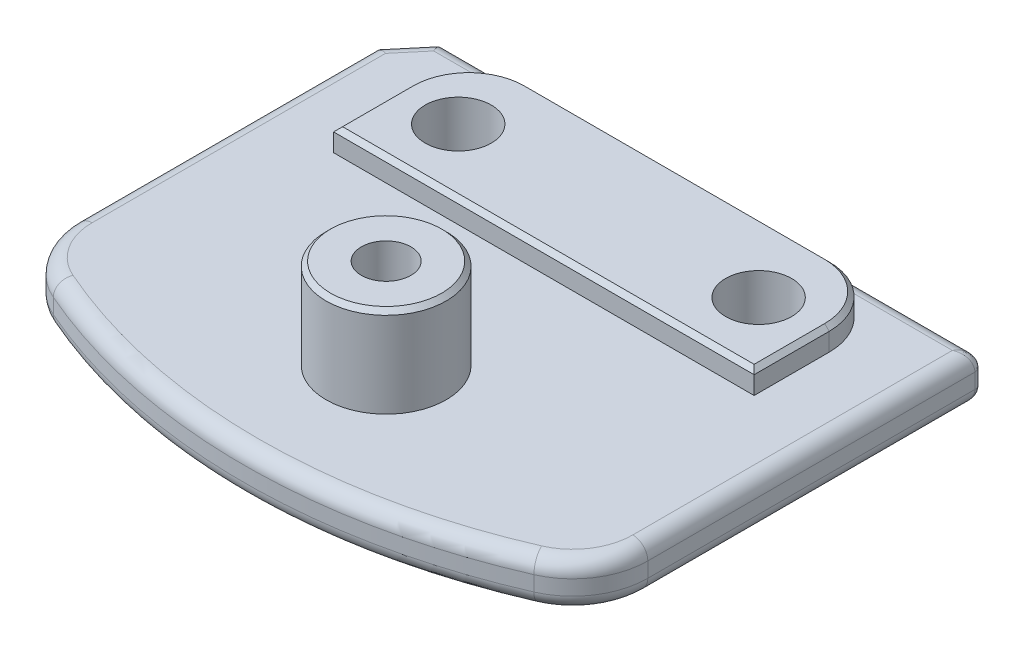
SolidWorks part; units mm, degrees
material "6061-T6 (SS)"
ref_plane "정면" through (0, 0, 0) normal (0, 0, 1) x (1, 0, 0)
ref_plane "윗면" through (0, 0, 0) normal (0, 1, 0) x (1, 0, 0)
ref_plane "우측면" through (0, 0, 0) normal (1, 0, 0) x (0, 0, -1)
sketch "스케치1" plane through (0, 0, 0) normal (0, 1, 0) x (1, 0, 0)
  line L0 (-10, 14.8) -> (10, 14.8) construction
  line L1 (0, 14.8) -> (0, 0) construction
  line L2 (-19, 10.5) -> (19, 10.5)
  line L3 (-10, 19.5) -> (10, 19.5)
  line L4 (0, 14.8) -> (0, 19.5) construction
  line L5 (-14, 15.5) -> (-14, 10.5)
  line L6 (14, 15.5) -> (14, 10.5)
  line L7 (-19, 20.7) -> (19, 20.7)
  line L8 (0, 19.5) -> (0, 20.7) construction
  line L11 (-19, 10.5) -> (-19, -4.6994)
  line L12 (-19, -9.5) -> (19, -9.5) construction
  line L13 (19, -4.6994) -> (19, 10.5)
  line L14 (-14, 10.5) -> (-19, 10.5)
  line L16 (-19, 10.5) -> (-19, 20.7)
  line L17 (19, 10.5) -> (19, 20.7)
  circle A0 centre (0, 0) radius 1.65
  circle A1 centre (-10, 14.8) radius 2.2
  circle A2 centre (10, 14.8) radius 2.2
  arc A3 (10, 19.5) -> (14, 15.5) centre (10, 15.5) cw
  arc A4 (-10, 19.5) -> (-14, 15.5) centre (-10, 15.5) ccw
  arc A7 (-19, -4.6994) -> (19, -4.6994) centre (0, 30.5) ccw
  circle A11 centre (-10, 14.8) radius 3.75
  circle A12 centre (10, 14.8) radius 3.75
  circle A13 centre (0, 0) radius 4
  point P10 (0, 10.5)
  point P18 (14, 19.5)
  point P21 (-14, 19.5)
  point P29 (-19, 20.7)
  dimension "D3" = 4.4
  dimension "D8" = 4
  dimension "D10" = 7.5
  dimension "D12" = 80
  dimension "D13" = 7.5
  dimension "D14" = 8
  dimension "D15" = 3.3
  dimension "D1" = 14.8
  dimension "D2" = 20
  dimension "D4" = 10.5
  dimension "D5" = 38
  dimension "D6" = 28
  dimension "D7" = 9
  dimension "D9" = 1.2
  dimension "D11" = 20
extrude "보스-돌출1" add sketch "스케치1" along normal blind 1.5 contours L3 A4 L5 L2 L6 A3 A1 A2 | A11 A1 | A12 A2 region at (0, 0, -14.9547) region at (-13.6439, 0, -14.8) region at (6.3561, 0, -14.8)
extrude "보스-돌출2" add sketch "스케치1<3>" against normal blind 3 contours L7 L2 L5 A4 L3 A3 L6 | L3 A4 L5 L2 L6 A3 A1 A2 | L11 A7 L13 L2 | L14 | A11 A1 | A12 A2 region at (-18.6065, 0, -15.6) region at (-16.5, 0, -10.0706) region at (0, 0, -14.9547) region at (-13.6439, 0, -14.8) region at (6.3561, 0, -14.8)
sketch "스케치1<3>" plane through (0, 0, 0) normal (0, 1, 0) x (1, 0, 0) same geometry as "스케치1"
extrude "보스-돌출3" add sketch "스케치1<5>" along normal blind 9 from surface contours A0 region at (-3.8869, 0, 0) starting at face at (0, -3, -6.8001)
sketch "스케치1<5>" plane through (0, 0, 0) normal (0, 1, 0) x (1, 0, 0) same geometry as "스케치1"
fillet "필렛6" radius 0.5 1 edges at (19, -1.5, -20.7)
fillet "필렛3" radius 5 2 edges at (-19, -1.5, 4.6994) (19, -1.5, 4.6994)
chamfer "모따기7" distance 2 angle 50 1 edges at (-19, -1.5, -20.7) first distance on face at (-0.25, -1.5, -20.7)
fillet "필렛5" radius 1 16 edges at (0.75, 0, -20.7) (19, 0, -9.311) (18.1833, 0, 4.3166) (0, 0, 9.5) (-18.1833, 0, 4.3166) (-19, 0, -8.3692) (18.1833, -3, 4.3166) (0.75, -3, -20.7) (-19, -3, -8.3692) (-18.1833, -3, 4.3166) (0, -3, 9.5) (19, -3, -9.311) (18.8536, 0, -20.5536) (18.8536, -3, -20.5536) (-18, 0, -19.5082) (-18, -3, -19.5082)
chamfer "모따기3" distance 0.3 angle 45 6 edges at (14, 1.5, -13) (12.8284, 1.5, -18.3284) (0, 1.5, -19.5) (0, 1.5, -10.5) (-14, 1.5, -13) (-12.8284, 1.5, -18.3284)
chamfer "모따기5" distance 0.3 angle 45 1 edges at (0, -3, 1.65)
extrude "컷-돌출1" cut sketch "스케치1<6>" along normal blind 1 from surface contours A12 A2 | A11 A1 region at (-13.6439, 0, -14.8) region at (6.3561, 0, -14.8) starting at face at (0, -3, 1.95)
sketch "스케치1<6>" plane through (0, 0, 0) normal (0, 1, 0) x (1, 0, 0) same geometry as "스케치1"
chamfer "모따기4" distance 0.3 angle 45 4 edges at (-10, -2, -12.6) (10, -2, -12.6) (-10, -3, -11.05) (10, -3, -11.05)
chamfer "모따기6" distance 0.3 angle 45 1 edges at (0, 6, 4)
